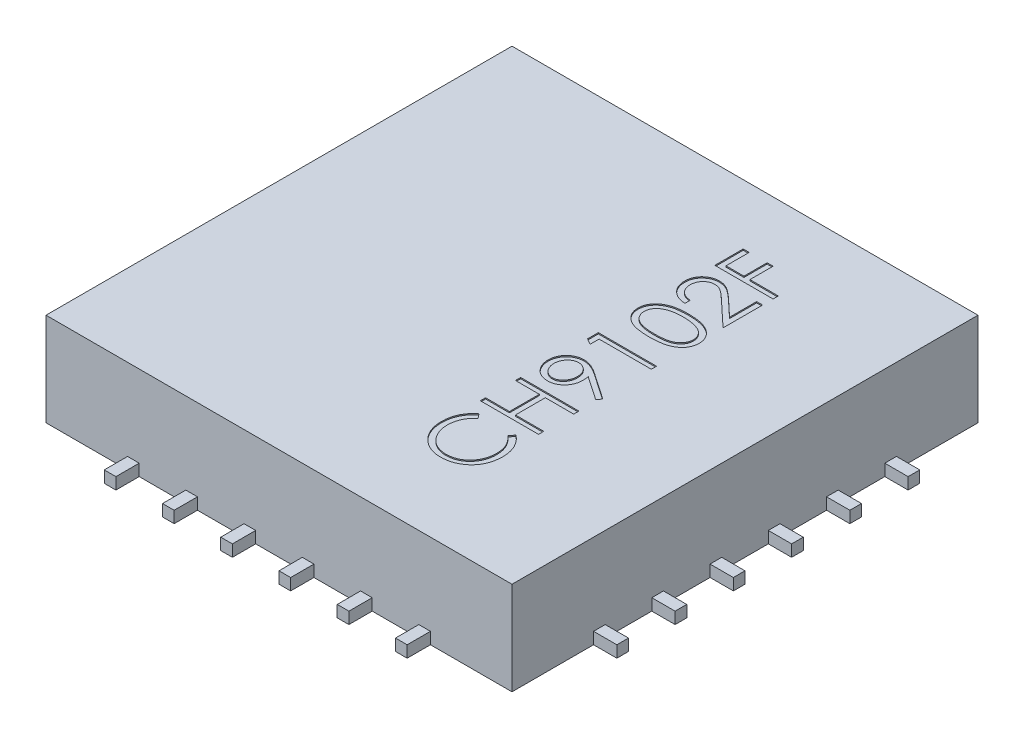
SolidWorks part; units mm, degrees
ref_plane "Front Plane" through (0, 0, 0) normal (0, 0, 1) x (1, 0, 0)
ref_plane "Top Plane" through (0, 0, 0) normal (0, 1, 0) x (1, 0, 0)
ref_plane "Right Plane" through (0, 0, 0) normal (1, 0, 0) x (0, 0, -1)
sketch "BaseS" plane through (0, 0, 0) normal (0, 1, 0) x (1, 0, 0)
  line L1 (-2, 2) -> (2, 2)
  line L2 (-2, 2) -> (-2, -2)
  line L3 (-2, -2) -> (2, -2)
  line L4 (2, 2) -> (2, -2)
  line L5 (-2, 2) -> (2, -2) construction
  line L6 (-2, -2) -> (2, 2) construction
  point P0 (0, 0)
  dimension "W" = 4
  dimension "L" = 4
extrude "Base" add sketch "BaseS" along normal blind 0.8
sketch "SolderConnectionS" plane through (0, 0, 0) normal (0, 1, 0) x (1, 0, 0)
  line L0 (2, -1.25) -> (2.2, -1.25)
  line L1 (2, -2) -> (2, 2) construction
  line L2 (2, -0.75) -> (2.2, -0.75)
  line L3 (2, -0.25) -> (2.2, -0.25)
  line L4 (2, 0.25) -> (2.2, 0.25)
  line L5 (2, 0.75) -> (2.2, 0.75)
  line L6 (2, 1.25) -> (2.2, 1.25)
  line L8 (2, -1.25) -> (2, -2) construction
  line L9 (2, 2) -> (2, 1.25) construction
  dimension "D1" = 6
  dimension "Length" = 0.2
  dimension "D2" = 0.75
  dimension "Pitch" = 0.5
extrude "SolderConnection" add sketch "SolderConnectionS" along normal blind 0.1 thin thin type mid plane wall 0.1
ref_axis "AxisSC" through (0, 0.84, 0) along (0, -1, 0)
pattern_circular "SC CP" count 4 over 360 about axis through (0, 0.84, 0) along (0, -1, 0) of "SolderConnection"
sketch "PartNoS" plane through (0, 0.8, 0) normal (0, 1, 0) x (1, 0, 0)
  line L0 (1, -1.4) -> (1, 2) construction
  line L1 (2, 2) -> (-2, 2) construction
  line L2 (-2, -2) -> (2, -2) construction
  line L3 (-2, 2) -> (-2, -2) construction
  text T0 "CH9102F" font "Century Gothic" height 0.5
  dimension "YDim" = 3
  dimension "XDim" = 0.6
extrude "PartNo" cut sketch "PartNoS" against normal blind 0.01
